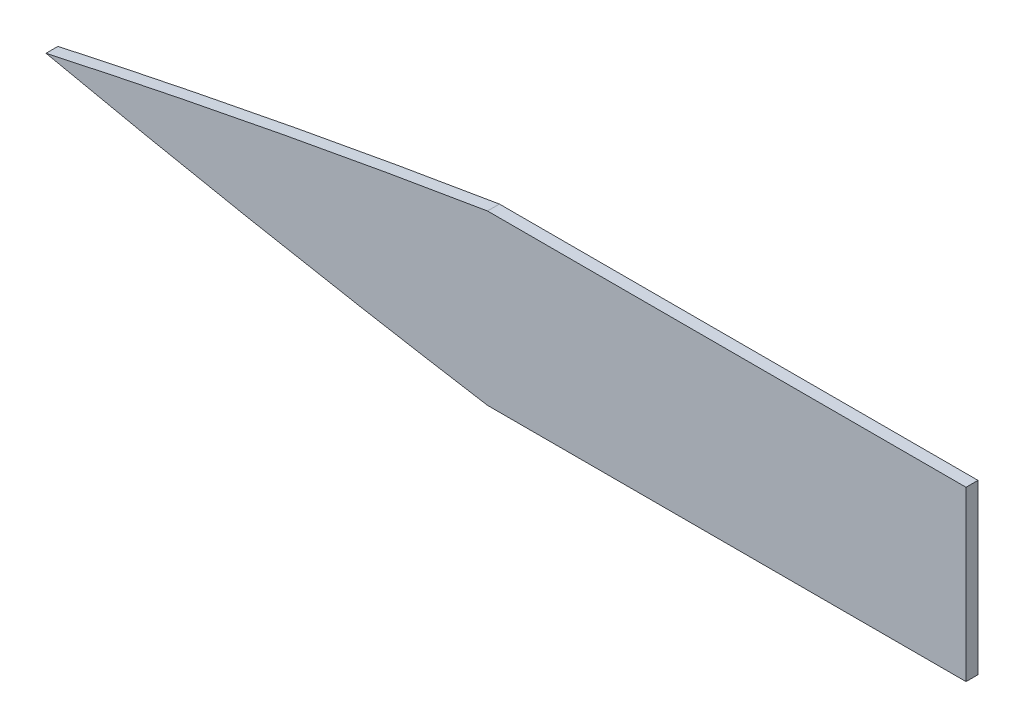
SolidWorks part; units mm, degrees
ref_plane "Front Plane" through (0, 0, 0) normal (0, 0, 1) x (1, 0, 0)
ref_plane "Top Plane" through (0, 0, 0) normal (0, 1, 0) x (1, 0, 0)
ref_plane "Right Plane" through (0, 0, 0) normal (1, 0, 0) x (0, 0, -1)
sketch "Sketch2" plane through (0, 0, 0) normal (0, 0, 1) x (1, 0, 0)
  line L0 (98.5029, 17.5888) -> (198.5029, 17.5888)
  line L1 (0, 0) -> (244.4547, 0) construction
  line L2 (98.5029, -17.5888) -> (198.5029, -17.5888)
  line L4 (198.5029, -17.5888) -> (198.5029, 17.5888)
  spline S0 degree 2 poles (6.2534, 0) (52.1488, 9.9754) (98.5029, 17.5888) knots 0 0 0 1 1 1
  spline S1 degree 2 poles (6.2534, 0) (52.1488, -9.9754) (98.5029, -17.5888) knots 0 0 0 1 1 1
  point P6 (0, 0)
  point P10 (0, 0)
  dimension "D1" = 100
extrude "Boss-Extrude1" add sketch "Sketch2" along normal blind 1.25 and the other way blind 1.25
